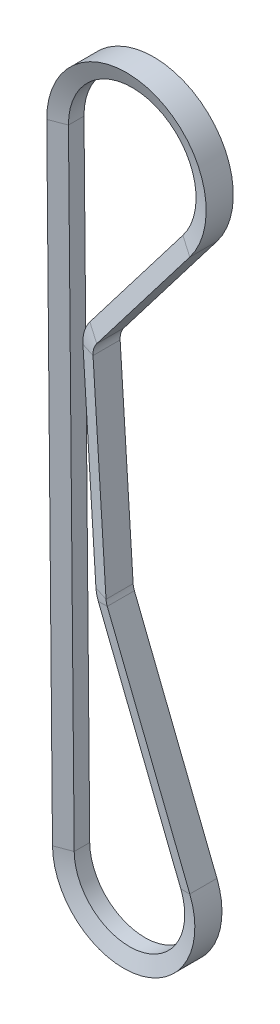
SolidWorks part; units mm, degrees
ref_plane "Front Plane" through (0, 0, 0) normal (0, 0, 1) x (1, 0, 0)
ref_plane "Top Plane" through (0, 0, 0) normal (0, 1, 0) x (1, 0, 0)
ref_plane "Right Plane" through (0, 0, 0) normal (1, 0, 0) x (0, 0, -1)
sketch "Sketch2" plane through (0, 0, 0) normal (0, 0, 1) x (1, 0, 0)
  line L0 (0, 0) -> (1, 0) construction
  line L1 (0, 0) -> (0, 1) construction
  line L9 (23.215, 202.9758) -> (-9.4709, 160.2861)
  line L10 (-10.7662, 156.023) -> (-6.2002, 84.168)
  line L11 (-5.7644, 82.2263) -> (23.2338, 9.2297)
  line L12 (-24.9989, -0.2292) -> (-27.0157, 219.7411)
  arc A4 (-27.0157, 219.7411) -> (23.215, 202.9758) centre (0.9832, 219.9978) cw
  arc A5 (-9.4709, 160.2861) -> (-10.7662, 156.023) centre (-4.429, 156.4257) ccw
  arc A6 (-6.2002, 84.168) -> (-5.7644, 82.2263) centre (0.137, 84.5707) ccw
  arc A7 (23.2338, 9.2297) -> (-24.9989, -0.2292) centre (0, 0) cw
ref_plane "Plane4" through (23.2338, 9.2297, 0) normal (0.3692, -0.9294, 0) x (0, 0, -1)
sketch "Sketch3" plane through (23.2338, 9.2297, 0) normal (0.3692, -0.9294, 0) x (0, 0, -1)
  line L0 (-4.7625, 0) -> (4.7625, 0)
  line L1 (-4.7625, 0) -> (-2.7286, -5.588)
  line L2 (-2.7286, -5.588) -> (2.7286, -5.588)
  line L3 (2.7286, -5.588) -> (4.7625, 0)
  line L4 (0, 0) -> (0, -5.588) construction
  dimension "D1" = 9.525
  dimension "D2" = 5.588
  dimension "D3" = 40
sweep "Sweep1" add profiles "Sketch3" path "Sketch2"
